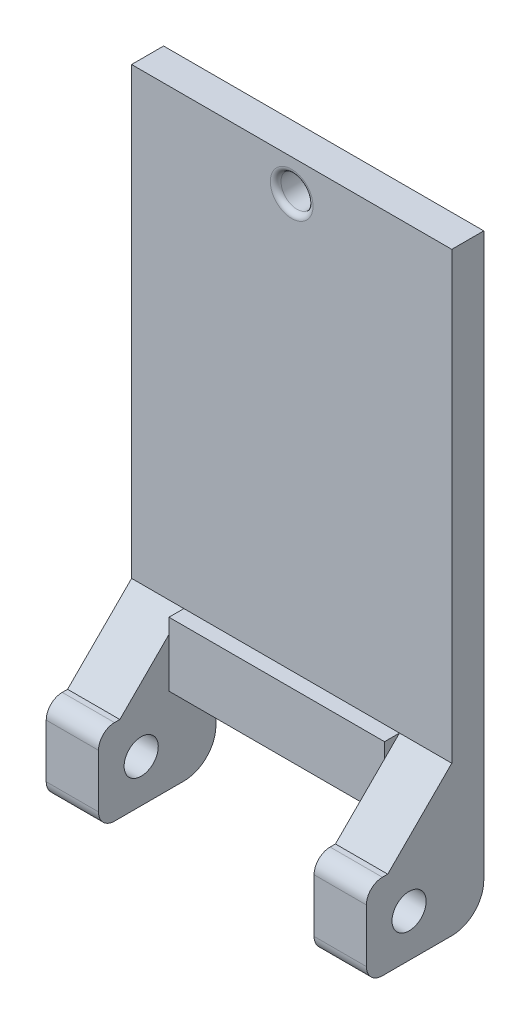
SolidWorks part; units mm, degrees
ref_plane "Front Plane" through (0, 0, 0) normal (0, 0, 1) x (1, 0, 0)
ref_plane "Top Plane" through (0, 0, 0) normal (0, 1, 0) x (1, 0, 0)
ref_plane "Right Plane" through (0, 0, 0) normal (1, 0, 0) x (0, 0, -1)
sketch "Sketch1" plane through (0, 0, 0) normal (0, 0, 1) x (1, 0, 0)
  line L1 (-15, -27.85) -> (15, -27.85)
  line L2 (-15, -27.85) -> (-15, 27.85)
  line L3 (-15, 27.85) -> (15, 27.85)
  line L4 (15, -27.85) -> (15, 27.85)
  line L5 (-15, -27.85) -> (15, 27.85) construction
  line L6 (-15, 27.85) -> (15, -27.85) construction
  point P0 (0, 0)
  dimension "D1" = 55.7
  dimension "D2" = 30
extrude "Boss-Extrude1" add sketch "Sketch1" along normal blind 3
sketch "Sketch2" plane through (0, 0, 3) normal (0, 0, 1) x (1, 0, 0)
  line L0 (0, -27.85) -> (0, 27.85) construction
  line L1 (15, 27.85) -> (-15, 27.85) construction
  line L3 (-15, -27.85) -> (-10.1, -27.85)
  line L4 (-15, -27.85) -> (-15, -19.85)
  line L5 (-15, -19.85) -> (-10.1, -19.85)
  line L6 (-10.1, -27.85) -> (-10.1, -19.85)
  point P6 (0, 0)
  dimension "D1" = 4.9
  dimension "D2" = 8
extrude "Boss-Extrude2" add sketch "Sketch2" along normal blind 8
sketch "Sketch3" plane through (-15, 0, 0) normal (-1, 0, 0) x (0, 0, 1)
  line L0 (11, -27.85) -> (0, -27.85) construction
  line L2 (3, 27.85) -> (3, -19.85) construction
  circle A0 centre (7, -23.85) radius 1.6
  dimension "D1" = 3.2
  dimension "D2" = 4
  dimension "D3" = 4
extrude "Cut-Extrude1" cut sketch "Sketch3" against normal through all
mirror "Mirror1" about plane through (0, 0, 0) normal (1, 0, 0) of "Cut-Extrude1", "Boss-Extrude2"
sketch "Sketch4" plane through (0, 0, 3) normal (0, 0, 1) x (1, 0, 0)
  line L1 (15, 27.85) -> (-15, 27.85) construction
  line L3 (0, 27.85) -> (0, 24.85) construction
  circle A0 centre (0, 24.85) radius 1.5
  dimension "D1" = 3
  dimension "D2" = 3
extrude "Cut-Extrude2" cut sketch "Sketch4" against normal blind 10 contours A0
fillet "Fillet3" radius 0.5 2 edges at (-1.5, 24.85, 0) (1.5, 24.85, 3)
fillet "Fillet4" radius 3 1 edges at (0, -27.85, 0)
sketch "Sketch5" plane through (0, 0, 3) normal (0, 0, 1) x (1, 0, 0)
  line L0 (10.1, -27.85) -> (10.1, -19.85) construction
  line L1 (-10.1, -27.85) -> (-10.1, -19.85) construction
  line L2 (10.1, -27.85) -> (10.1, -19.85)
  line L3 (-10.1, -27.85) -> (-10.1, -19.85)
  line L4 (-10.1, -19.85) -> (10.1, -19.85)
  line L5 (10.1, -27.85) -> (10.1, -30.3306)
  line L6 (10.1, -30.3306) -> (-10.1, -30.3306)
  line L7 (-10.1, -30.3306) -> (-10.1, -27.85)
extrude "Cut-Extrude4" cut sketch "Sketch5" against normal blind 10 and the other way through all
fillet "Fillet5" radius 1.5 4 edges at (-12.55, -27.85, 11) (-12.55, -19.85, 11) (12.55, -19.85, 11) (12.55, -27.85, 11)
chamfer "Chamfer1" distance 6 angle 45 2 edges at (-12.55, -19.85, 3) (12.55, -19.85, 3)
sketch "Sketch6" plane through (0, 0, 3) normal (0, 0, 1) x (1, 0, 0)
  line L0 (-10.1, -13.85) -> (10.1, -13.85)
  line L1 (10.1, -19.85) -> (10.1, -13.85) construction
  line L2 (-10.1, -19.85) -> (10.1, -19.85) construction
  line L3 (-10.1, -13.85) -> (-10.1, -19.85) construction
  line L4 (10.1, -19.85) -> (10.1, -13.85)
  line L5 (-10.1, -19.85) -> (10.1, -19.85)
  line L6 (-10.1, -13.85) -> (-10.1, -19.85)
extrude "Boss-Extrude3" add sketch "Sketch6" along normal blind 1.4
